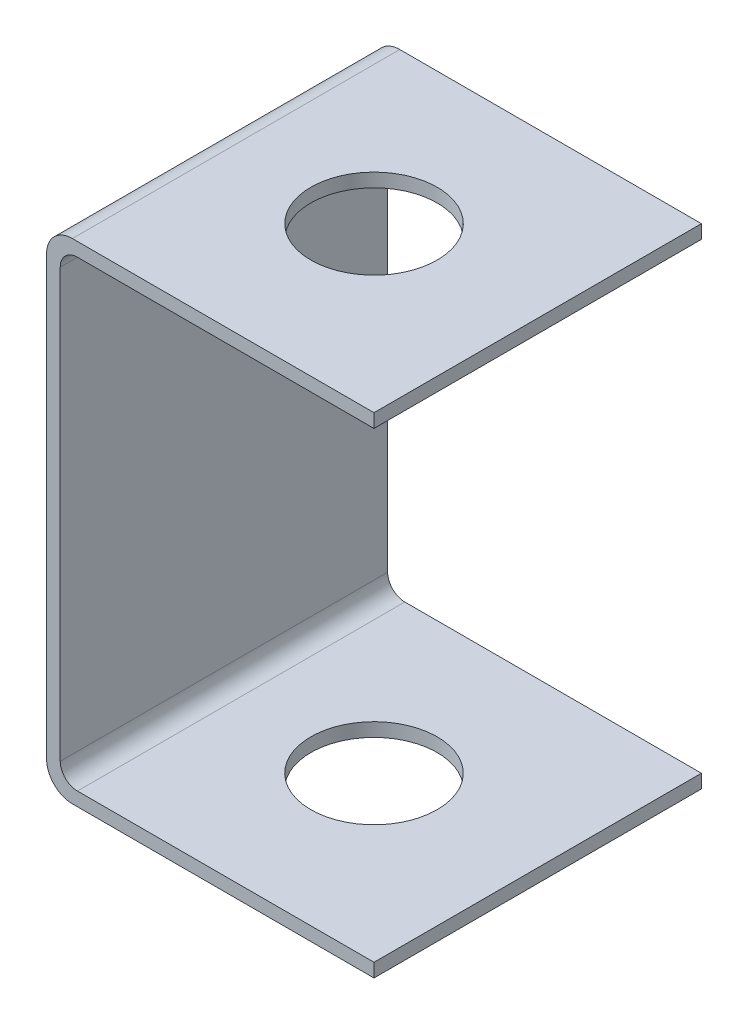
SolidWorks part; units mm, degrees
material "Alumina"
ref_plane "Front Plane" through (0, 0, 0) normal (0, 0, 1) x (1, 0, 0)
ref_plane "Top Plane" through (0, 0, 0) normal (0, 1, 0) x (1, 0, 0)
ref_plane "Right Plane" through (0, 0, 0) normal (1, 0, 0) x (0, 0, -1)
sketch "Sketch1" plane through (0, 0, 0) normal (0, 0, 1) x (1, 0, 0)
  line L0 (-17.4625, 55.3875) -> (19.05, 55.3875)
  line L1 (19.05, 55.3875) -> (19.05, 56.975)
  line L2 (19.05, 56.975) -> (-19.05, 56.975)
  line L3 (-19.05, 56.975) -> (-19.05, 0)
  line L4 (-19.05, 0) -> (19.05, 0)
  line L5 (19.05, 0) -> (19.05, 1.5875)
  line L6 (19.05, 1.5875) -> (-17.4625, 1.5875)
  line L7 (-17.4625, 1.5875) -> (-17.4625, 55.3875)
  point P7 (0, 0)
  dimension "D1" = 1.5875
  dimension "D2" = 1.5875
  dimension "D3" = 1.5875
  dimension "D4" = 38.1
  dimension "D5" = 53.8
extrude "Boss-Extrude1" add sketch "Sketch1" along normal blind 38.1
sketch "Sketch3" plane through (0, 0, 0) normal (0, 1, 0) x (1, 0, 0)
  circle A0 centre (0, -19.05) radius 7.35
  dimension "D2" = 14.7
  dimension "D1" = 19.05
extrude "Cut-Extrude1" cut sketch "Sketch3" along normal through all
fillet "Fillet1" radius 2 2 edges at (-17.4625, 1.5875, 19.05) (-17.4625, 55.3875, 19.05)
fillet "Fillet2" radius 3 2 edges at (-19.05, 0, 19.05) (-19.05, 56.975, 19.05)
equation "\"boltDiameter\"= 1in / 2"
equation "\"sleeveHeight\"= 2in"
equation "\"bracketThickness\"= 1in / 16"
equation "\"D1@Sketch1\"=\"bracketThickness\""
equation "\"D2@Sketch1\"=\"bracketThickness\""
equation "\"D3@Sketch1\"=\"bracketThickness\""
equation "\"D5@Sketch1\"=\"sleeveHeight\"+3mm"
equation "\"D2@Sketch3\"=\"boltDiameter\"+2mm"
